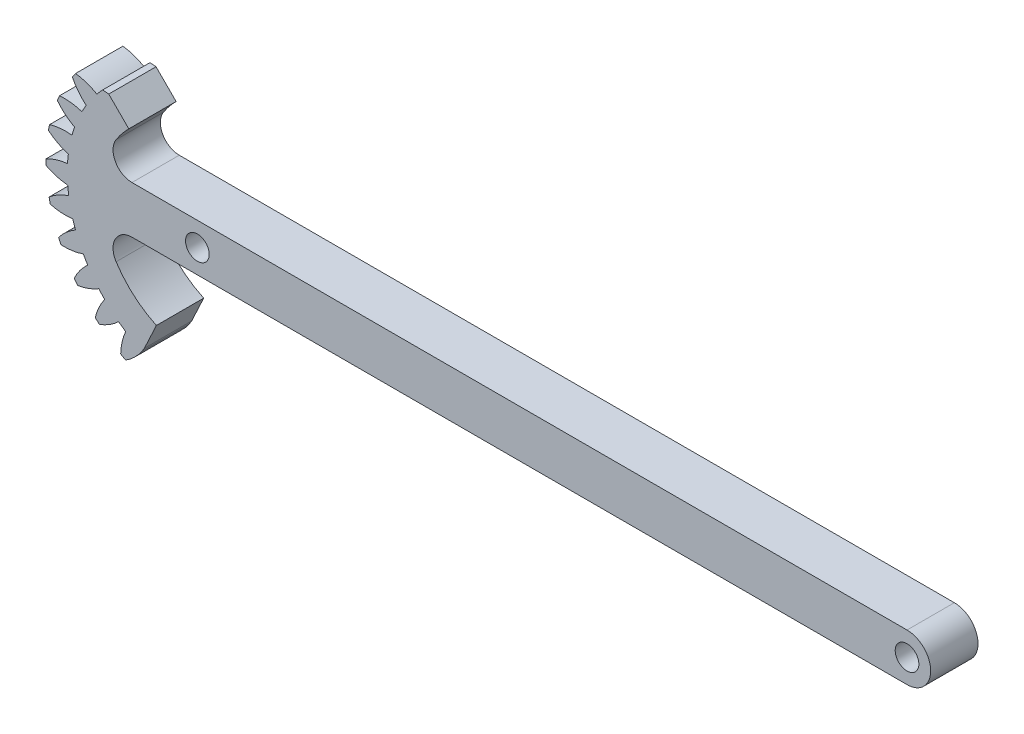
SolidWorks part; units mm, degrees
material "ABS"
ref_plane "Front Plane" through (0, 0, 0) normal (0, 0, 1) x (1, 0, 0)
ref_plane "Top Plane" through (0, 0, 0) normal (0, 1, 0) x (1, 0, 0)
ref_plane "Right Plane" through (0, 0, 0) normal (1, 0, 0) x (0, 0, -1)
ref_axis "X" through (-88.99, 0, 0) along (1, 0, 0)
ref_axis "Y" through (0, 55, 0) along (0, -1, 0)
ref_axis "Z" through (0, 0, -88.99) along (0, 0, 1)
sketch "Sketch1" plane through (0, 0, 0) normal (0, 0, 1) x (1, 0, 0)
  line L0 (0, 0) -> (150, 0) construction
  line L1 (0, 5) -> (150, 5)
  line L2 (0, -5) -> (150, -5)
  arc A0 (0, 5) -> (0, -5) centre (0, 0) ccw
  arc A1 (150, -5) -> (150, 5) centre (150, 0) ccw
  circle A2 centre (0, 0) radius 2.5
  circle A3 centre (150, 0) radius 2.5
  point P3 (75, 0)
  dimension "D1" = 5
  dimension "D3" = 5
  dimension "D2" = 150
extrude "Boss-Extrude1" add sketch "Sketch1" along normal mid plane 10
sketch "Sketch2" plane through (0, 0, 0) normal (0, 0, 1) x (1, 0, 0)
  line L0 (0, 5) -> (-19.8809, 5)
  line L1 (0, -5) -> (-19.8809, -5)
  line L2 (0, 0) -> (-14.4957, 14.4957) construction
  line L3 (0, 0) -> (-8.6637, -18.5793) construction
  line L4 (0, 0) -> (150, 0) construction
  line L5 (-14.4957, 14.4957) -> (-18.7383, 18.7383)
  line L6 (-8.6637, -18.5793) -> (-11.1994, -24.0172)
  arc A0 (-19.8809, 5) -> (-14.4957, 14.4957) centre (0, 0) cw
  arc A1 (-19.8809, -5) -> (-8.6637, -18.5793) centre (0, 0) ccw
  arc A3 (-18.7383, 18.7383) -> (-11.1994, -24.0172) centre (0, 0) ccw
  arc A4 (0, 5) -> (0, -5) centre (0, 0) ccw construction
  arc A5 (0, 5) -> (0, -5) centre (0, 0) ccw
  dimension "D1" = 135
  dimension "D3" = 20.5
  dimension "D2" = 110
  dimension "D4" = 6
extrude "Boss-Extrude2" add sketch "Sketch2" along normal up to surface and the other way up to surface up to face at (2.5, 0, 5) other way up to face at (75, 0, -5)
fillet "Fillet1" radius 4 2 edges at (-19.8809, 5, 0) (-19.8809, -5, 0)
sketch "Sketch3" plane through (0, 0, 0) normal (0, 0, 1) x (1, 0, 0)
  line L0 (-20.0217, 18.8501) -> (-18.7383, 18.7383)
  line L1 (-11.7405, -24.8668) -> (-11.1994, -24.0172)
  arc A1 (-18.7383, 18.7383) -> (-11.1994, -24.0172) centre (0, 0) ccw construction
  arc A2 (-18.7383, 18.7383) -> (-11.1994, -24.0172) centre (0, 0) ccw
  arc A121 (-31.9856, -0.9598) -> (-27.4055, -2.2658) centre (-26.4703, 9.6977) ccw
  arc A122 (-27.4055, -2.2658) -> (-27.1931, -4.0906) centre (0, 0) ccw
  arc A123 (-27.1931, -4.0906) -> (-31.3506, -6.4139) centre (-23.5345, -15.5193) ccw
  arc A124 (-31.3506, -6.4139) -> (-31.0871, -7.589) centre (0, 0) ccw
  arc A125 (-31.0871, -7.589) -> (-26.3355, -7.9142) centre (-27.9081, 3.9823) ccw
  arc A126 (-26.3355, -7.9142) -> (-25.7483, -9.655) centre (0, 0) ccw
  arc A127 (-25.7483, -9.655) -> (-29.332, -12.7919) centre (-19.7936, -20.0732) ccw
  arc A128 (-29.332, -12.7919) -> (-28.8299, -13.8865) centre (0, 0) ccw
  arc A129 (-28.8299, -13.8865) -> (-24.1146, -13.2167) centre (-28.1262, -1.9071) ccw
  arc A130 (-24.1146, -13.2167) -> (-23.1783, -14.7974) centre (0, 0) ccw
  arc A131 (-23.1783, -14.7974) -> (-26.0315, -18.6108) centre (-15.1876, -23.7499) ccw
  arc A132 (-26.0315, -18.6108) -> (-25.3128, -19.5771) centre (0, 0) ccw
  arc A133 (-25.3128, -19.5771) -> (-20.8397, -17.9416) centre (-27.1151, -7.7132) ccw
  arc A134 (-20.8397, -17.9416) -> (-19.5953, -19.293) centre (0, 0) ccw
  arc A135 (-19.5953, -19.293) -> (-21.5932, -23.6164) centre (-9.9178, -26.3886) ccw
  arc A136 (-21.5932, -23.6164) -> (-20.6893, -24.4121) centre (0, 0) ccw
  arc A137 (-20.6893, -24.4121) -> (-16.654, -21.8824) centre (-24.9189, -13.1822) ccw
  arc A138 (-16.654, -21.8824) -> (-15.1558, -22.9455) centre (0, 0) ccw
  arc A139 (-15.1558, -22.9455) -> (-16.2112, -27.5898) centre (-4.2146, -27.874) ccw
  arc A140 (-16.2112, -27.5898) -> (-15.1616, -28.1802) centre (0, 0) ccw
  arc A141 (-15.1616, -28.1802) -> (-11.7405, -24.8668) centre (-21.6336, -18.0751) ccw
  arc A142 (-11.7405, -24.8668) -> (-10.054, -25.5952) centre (0, 0) ccw
  arc A143 (-10.054, -25.5952) -> (-10.1207, -30.3574) centre (1.6728, -28.1411) ccw
  arc A144 (-10.1207, -30.3574) -> (-8.9713, -30.7167) centre (0, 0) ccw
  arc A145 (-8.9713, -30.7167) -> (-6.3138, -26.7643) centre (-17.4028, -22.178) ccw
  arc A146 (-6.3138, -26.7643) -> (-4.5127, -27.1262) centre (0, 0) ccw
  arc A147 (-4.5127, -27.1262) -> (-3.5879, -31.7982) centre (7.4872, -27.1783) ccw
  arc A148 (-3.5879, -31.7982) -> (-2.3889, -31.9107) centre (0, 0) ccw
  arc A149 (-2.3889, -31.9107) -> (-0.6113, -27.4922) centre (-12.4115, -25.3116) ccw
  arc A150 (-0.6113, -27.4922) -> (1.2257, -27.4717) centre (0, 0) ccw
  arc A151 (1.2257, -27.4717) -> (3.1017, -31.8493) centre (12.9742, -25.0278) ccw
  arc A152 (3.1017, -31.8493) -> (4.2979, -31.7101) centre (0, 0) ccw
  arc A153 (4.2979, -31.7101) -> (5.1181, -27.0185) centre (-6.8777, -27.3389) ccw
  arc A154 (5.1181, -27.0185) -> (6.9106, -26.6165) centre (0, 0) ccw
  arc A155 (6.9106, -26.6165) -> (9.6558, -30.5085) centre (17.8943, -21.7834) ccw
  arc A156 (9.6558, -30.5085) -> (10.7969, -30.1235) centre (0, 0) ccw
  arc A157 (10.7969, -30.1235) -> (10.6237, -25.364) centre (-1.0433, -28.1715) ccw
  arc A158 (10.6237, -25.364) -> (12.2935, -24.5981) centre (0, 0) ccw
  arc A159 (12.2935, -24.5981) -> (15.7879, -27.8342) centre (22.0323, -17.5869) ccw
  arc A160 (15.7879, -27.8342) -> (16.824, -27.2205) centre (0, 0) ccw
  arc A161 (16.824, -27.2205) -> (15.665, -22.6009) centre (4.8367, -27.7728) ccw
  arc A162 (15.665, -22.6009) -> (17.1391, -21.5046) centre (0, 0) ccw
  arc A163 (17.1391, -21.5046) -> (21.2299, -23.9435) centre (25.2073, -12.6218) ccw
  arc A164 (21.2299, -23.9435) -> (22.1158, -23.1277) centre (0, 0) ccw
  arc A165 (22.1158, -23.1277) -> (20.0217, -18.8501) centre (10.5053, -26.1603) ccw
  arc A166 (20.0217, -18.8501) -> (21.2356, -17.4712) centre (0, 0) ccw
  arc A167 (21.2356, -17.4712) -> (25.7441, -19.0063) centre (27.2807, -7.1051) ccw
  arc A168 (25.7441, -19.0063) -> (26.441, -18.0242) centre (0, 0) ccw
  arc A169 (26.441, -18.0242) -> (23.5033, -14.2755) centre (15.7147, -23.4044) ccw
  arc A170 (23.5033, -14.2755) -> (24.404, -12.6743) centre (0, 0) ccw
  arc A171 (24.404, -12.6743) -> (29.1332, -13.2385) centre (28.1618, -1.2779) ccw
  arc A172 (29.1332, -13.2385) -> (29.6107, -12.1329) centre (0, 0) ccw
  arc A173 (29.6107, -12.1329) -> (25.9578, -9.0769) centre (20.2374, -19.6257) ccw
  arc A174 (25.9578, -9.0769) -> (26.5059, -7.3235) centre (0, 0) ccw
  arc A175 (26.5059, -7.3235) -> (31.249, -6.8921) centre (27.8121, 4.6052) ccw
  arc A176 (31.249, -6.8921) -> (31.4862, -5.7114) centre (0, 0) ccw
  arc A177 (31.4862, -5.7114) -> (27.2777, -3.4816) centre (23.8756, -14.9892) ccw
  arc A178 (27.2777, -3.4816) -> (27.4493, -1.6526) centre (0, 0) ccw
  arc A179 (27.4493, -1.6526) -> (31.9991, -0.2444) centre (26.2468, 10.2871) ccw
  arc A180 (31.9991, -0.2444) -> (31.9856, 0.9598) centre (0, 0) ccw
  arc A181 (31.9856, 0.9598) -> (27.4055, 2.2658) centre (26.4703, -9.6977) ccw
  arc A182 (27.4055, 2.2658) -> (27.1931, 4.0906) centre (0, 0) ccw
  arc A183 (27.1931, 4.0906) -> (31.3506, 6.4139) centre (23.5345, 15.5193) ccw
  arc A184 (31.3506, 6.4139) -> (31.0871, 7.589) centre (0, 0) ccw
  arc A185 (31.0871, 7.589) -> (26.3355, 7.9142) centre (27.9081, -3.9823) ccw
  arc A186 (26.3355, 7.9142) -> (25.7483, 9.655) centre (0, 0) ccw
  arc A187 (25.7483, 9.655) -> (29.332, 12.7919) centre (19.7936, 20.0732) ccw
  arc A188 (29.332, 12.7919) -> (28.8299, 13.8865) centre (0, 0) ccw
  arc A189 (28.8299, 13.8865) -> (24.1146, 13.2167) centre (28.1262, 1.9071) ccw
  arc A190 (24.1146, 13.2167) -> (23.1783, 14.7974) centre (0, 0) ccw
  arc A191 (23.1783, 14.7974) -> (26.0315, 18.6108) centre (15.1876, 23.7499) ccw
  arc A192 (26.0315, 18.6108) -> (25.3128, 19.5771) centre (0, 0) ccw
  arc A193 (25.3128, 19.5771) -> (20.8397, 17.9416) centre (27.1151, 7.7132) ccw
  arc A194 (20.8397, 17.9416) -> (19.5953, 19.293) centre (0, 0) ccw
  arc A195 (19.5953, 19.293) -> (21.5932, 23.6164) centre (9.9178, 26.3886) ccw
  arc A196 (21.5932, 23.6164) -> (20.6893, 24.4121) centre (0, 0) ccw
  arc A197 (20.6893, 24.4121) -> (16.654, 21.8824) centre (24.9189, 13.1822) ccw
  arc A198 (16.654, 21.8824) -> (15.1558, 22.9455) centre (0, 0) ccw
  arc A199 (15.1558, 22.9455) -> (16.2112, 27.5898) centre (4.2146, 27.874) ccw
  arc A200 (16.2112, 27.5898) -> (15.1616, 28.1802) centre (0, 0) ccw
  arc A201 (15.1616, 28.1802) -> (11.7405, 24.8668) centre (21.6336, 18.0751) ccw
  arc A202 (11.7405, 24.8668) -> (10.054, 25.5952) centre (0, 0) ccw
  arc A203 (10.054, 25.5952) -> (10.1207, 30.3574) centre (-1.6728, 28.1411) ccw
  arc A204 (10.1207, 30.3574) -> (8.9713, 30.7167) centre (0, 0) ccw
  arc A205 (8.9713, 30.7167) -> (6.3138, 26.7643) centre (17.4028, 22.178) ccw
  arc A206 (6.3138, 26.7643) -> (4.5127, 27.1262) centre (0, 0) ccw
  arc A207 (4.5127, 27.1262) -> (3.5879, 31.7982) centre (-7.4872, 27.1783) ccw
  arc A208 (3.5879, 31.7982) -> (2.3889, 31.9107) centre (0, 0) ccw
  arc A209 (2.3889, 31.9107) -> (0.6113, 27.4922) centre (12.4115, 25.3116) ccw
  arc A210 (0.6113, 27.4922) -> (-1.2257, 27.4717) centre (0, 0) ccw
  arc A211 (-1.2257, 27.4717) -> (-3.1017, 31.8493) centre (-12.9742, 25.0278) ccw
  arc A212 (-3.1017, 31.8493) -> (-4.2979, 31.7101) centre (0, 0) ccw
  arc A213 (-4.2979, 31.7101) -> (-5.1181, 27.0185) centre (6.8777, 27.3389) ccw
  arc A214 (-5.1181, 27.0185) -> (-6.9106, 26.6165) centre (0, 0) ccw
  arc A215 (-6.9106, 26.6165) -> (-9.6558, 30.5085) centre (-17.8943, 21.7834) ccw
  arc A216 (-9.6558, 30.5085) -> (-10.7969, 30.1235) centre (0, 0) ccw
  arc A217 (-10.7969, 30.1235) -> (-10.6237, 25.364) centre (1.0433, 28.1715) ccw
  arc A218 (-10.6237, 25.364) -> (-12.2935, 24.5981) centre (0, 0) ccw
  arc A219 (-12.2935, 24.5981) -> (-15.7879, 27.8342) centre (-22.0323, 17.5869) ccw
  arc A220 (-15.7879, 27.8342) -> (-16.824, 27.2205) centre (0, 0) ccw
  arc A221 (-16.824, 27.2205) -> (-15.665, 22.6009) centre (-4.8367, 27.7728) ccw
  arc A222 (-15.665, 22.6009) -> (-17.1391, 21.5046) centre (0, 0) ccw
  arc A223 (-17.1391, 21.5046) -> (-21.2299, 23.9435) centre (-25.2073, 12.6218) ccw
  arc A224 (-21.2299, 23.9435) -> (-22.1158, 23.1277) centre (0, 0) ccw
  arc A225 (-22.1158, 23.1277) -> (-20.0217, 18.8501) centre (-10.5053, 26.1603) ccw
  arc A226 (-20.0217, 18.8501) -> (-21.2356, 17.4712) centre (0, 0) ccw
  arc A227 (-21.2356, 17.4712) -> (-25.7441, 19.0063) centre (-27.2807, 7.1051) ccw
  arc A228 (-25.7441, 19.0063) -> (-26.441, 18.0242) centre (0, 0) ccw
  arc A229 (-26.441, 18.0242) -> (-23.5033, 14.2755) centre (-15.7147, 23.4044) ccw
  arc A230 (-23.5033, 14.2755) -> (-24.404, 12.6743) centre (0, 0) ccw
  arc A231 (-24.404, 12.6743) -> (-29.1332, 13.2385) centre (-28.1618, 1.2779) ccw
  arc A232 (-29.1332, 13.2385) -> (-29.6107, 12.1329) centre (0, 0) ccw
  arc A233 (-29.6107, 12.1329) -> (-25.9578, 9.0769) centre (-20.2374, 19.6257) ccw
  arc A234 (-25.9578, 9.0769) -> (-26.5059, 7.3235) centre (0, 0) ccw
  arc A235 (-26.5059, 7.3235) -> (-31.249, 6.8921) centre (-27.8121, -4.6052) ccw
  arc A236 (-31.249, 6.8921) -> (-31.4862, 5.7114) centre (0, 0) ccw
  arc A237 (-31.4862, 5.7114) -> (-27.2777, 3.4816) centre (-23.8756, 14.9892) ccw
  arc A238 (-27.2777, 3.4816) -> (-27.4493, 1.6526) centre (0, 0) ccw
  arc A239 (-27.4493, 1.6526) -> (-31.9991, 0.2444) centre (-26.2468, -10.2871) ccw
  arc A240 (-31.9991, 0.2444) -> (-31.9856, -0.9598) centre (0, 0) ccw
  arc A241 (-31.9856, -0.9598) -> (-27.4055, -2.2658) centre (-26.4703, 9.6977) ccw
  arc A242 (-27.4055, -2.2658) -> (-27.1931, -4.0906) centre (0, 0) ccw
  arc A243 (-27.1931, -4.0906) -> (-31.3506, -6.4139) centre (-23.5345, -15.5193) ccw
  arc A244 (-31.3506, -6.4139) -> (-31.0871, -7.589) centre (0, 0) ccw
  arc A245 (-31.0871, -7.589) -> (-26.3355, -7.9142) centre (-27.9081, 3.9823) ccw
  arc A246 (-26.3355, -7.9142) -> (-25.7483, -9.655) centre (0, 0) ccw
  arc A247 (-25.7483, -9.655) -> (-29.332, -12.7919) centre (-19.7936, -20.0732) ccw
  arc A248 (-29.332, -12.7919) -> (-28.8299, -13.8865) centre (0, 0) ccw
  arc A249 (-28.8299, -13.8865) -> (-24.1146, -13.2167) centre (-28.1262, -1.9071) ccw
  arc A250 (-24.1146, -13.2167) -> (-23.1783, -14.7974) centre (0, 0) ccw
  arc A251 (-23.1783, -14.7974) -> (-26.0315, -18.6108) centre (-15.1876, -23.7499) ccw
  arc A252 (-26.0315, -18.6108) -> (-25.3128, -19.5771) centre (0, 0) ccw
  arc A253 (-25.3128, -19.5771) -> (-20.8397, -17.9416) centre (-27.1151, -7.7132) ccw
  arc A254 (-20.8397, -17.9416) -> (-19.5953, -19.293) centre (0, 0) ccw
  arc A255 (-19.5953, -19.293) -> (-21.5932, -23.6164) centre (-9.9178, -26.3886) ccw
  arc A256 (-21.5932, -23.6164) -> (-20.6893, -24.4121) centre (0, 0) ccw
  arc A257 (-20.6893, -24.4121) -> (-16.654, -21.8824) centre (-24.9189, -13.1822) ccw
  arc A258 (-16.654, -21.8824) -> (-15.1558, -22.9455) centre (0, 0) ccw
  arc A259 (-15.1558, -22.9455) -> (-16.2112, -27.5898) centre (-4.2146, -27.874) ccw
  arc A260 (-16.2112, -27.5898) -> (-15.1616, -28.1802) centre (0, 0) ccw
  arc A261 (-15.1616, -28.1802) -> (-11.7405, -24.8668) centre (-21.6336, -18.0751) ccw
  arc A346 (-20.0217, 18.8501) -> (-21.2356, 17.4712) centre (0, 0) ccw
  arc A347 (-21.2356, 17.4712) -> (-25.7441, 19.0063) centre (-27.2807, 7.1051) ccw
  arc A348 (-25.7441, 19.0063) -> (-26.441, 18.0242) centre (0, 0) ccw
  arc A349 (-26.441, 18.0242) -> (-23.5033, 14.2755) centre (-15.7147, 23.4044) ccw
  arc A350 (-23.5033, 14.2755) -> (-24.404, 12.6743) centre (0, 0) ccw
  arc A351 (-24.404, 12.6743) -> (-29.1332, 13.2385) centre (-28.1618, 1.2779) ccw
  arc A352 (-29.1332, 13.2385) -> (-29.6107, 12.1329) centre (0, 0) ccw
  arc A353 (-29.6107, 12.1329) -> (-25.9578, 9.0769) centre (-20.2374, 19.6257) ccw
  arc A354 (-25.9578, 9.0769) -> (-26.5059, 7.3235) centre (0, 0) ccw
  arc A355 (-26.5059, 7.3235) -> (-31.249, 6.8921) centre (-27.8121, -4.6052) ccw
  arc A356 (-31.249, 6.8921) -> (-31.4862, 5.7114) centre (0, 0) ccw
  arc A357 (-31.4862, 5.7114) -> (-27.2777, 3.4816) centre (-23.8756, 14.9892) ccw
  arc A358 (-27.2777, 3.4816) -> (-27.4493, 1.6526) centre (0, 0) ccw
  arc A359 (-27.4493, 1.6526) -> (-31.9991, 0.2444) centre (-26.2468, -10.2871) ccw
  arc A360 (-31.9991, 0.2444) -> (-31.9856, -0.9598) centre (0, 0) ccw
  dimension "D1" = 0
extrude "Boss-Extrude3" add sketch "Sketch3" along normal up to surface and the other way up to surface up to face at (2.5, 0, 5) other way up to face at (17.4467, -1.1852, -5)
